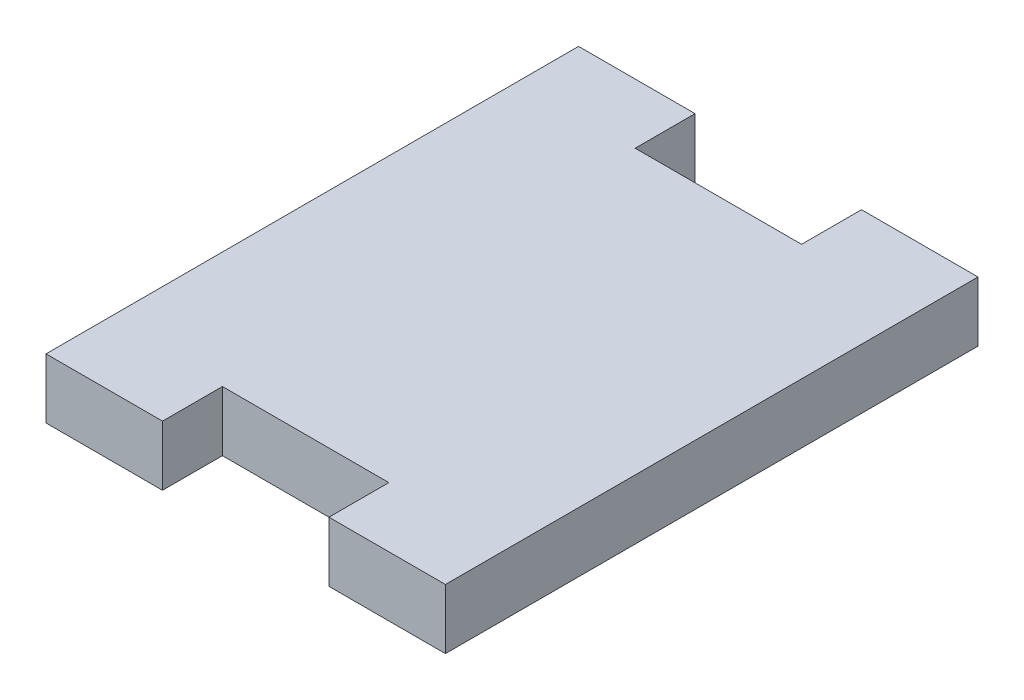
SolidWorks part; units mm, degrees
ref_plane "Front Plane" through (0, 0, 0) normal (0, 0, 1) x (1, 0, 0)
ref_plane "Top Plane" through (0, 0, 0) normal (0, 1, 0) x (1, 0, 0)
ref_plane "Right Plane" through (0, 0, 0) normal (1, 0, 0) x (0, 0, -1)
sketch "Sketch1" plane through (0, 0, 0) normal (0, 1, 0) x (1, 0, 0)
  line L0 (-363.1089, 480) -> (-363.1089, -480)
  line L1 (-363.1089, -480) -> (-303.1089, -480)
  line L2 (-303.1089, -480) -> (-303.1089, -400)
  line L3 (-303.1089, -400) -> (303.1089, -50)
  line L4 (303.1089, -50) -> (1036.8911, -50)
  line L5 (1036.8911, -50) -> (1036.8911, 50) construction
  line L6 (1036.8911, 50) -> (303.1089, 50)
  line L7 (303.1089, 50) -> (-303.1089, 400)
  line L8 (-303.1089, 400) -> (-303.1089, 480)
  line L9 (-303.1089, 480) -> (-363.1089, 480)
  line L10 (-363.1089, 0) -> (1036.8911, 0) construction
  line L11 (0, 225) -> (0, -225) construction
  line L14 (1036.8911, 50) -> (1066.8911, 50)
  line L15 (1036.8911, 50) -> (1036.8911, -50) construction
  line L16 (1036.8911, -50) -> (1066.8911, -50)
  line L17 (1066.8911, 50) -> (1066.8911, -50)
  dimension "D1" = 960
  dimension "D2" = 60
  dimension "D3" = 100
  dimension "D4" = 1400
  dimension "D5" = 150
  dimension "D6" = 80
  dimension "D7" = 30
extrude "Boss-Extrude1" add sketch "Sketch1" along normal blind 9
sketch "Sketch2" plane through (0, 9, 0) normal (0, 1, 0) x (1, 0, 0)
  line L1 (-363.1089, 480) -> (-303.1089, 480)
  line L2 (-363.1089, 480) -> (-363.1089, 400)
  line L3 (-363.1089, 400) -> (-303.1089, 400)
  line L4 (-303.1089, 480) -> (-303.1089, 400)
  line L5 (-363.1089, -480) -> (-303.1089, -480)
  line L6 (-363.1089, -480) -> (-363.1089, -400)
  line L7 (-363.1089, -400) -> (-303.1089, -400)
  line L8 (-303.1089, -480) -> (-303.1089, -400)
extrude "Boss-Extrude2" add sketch "Sketch2" along normal blind 500
sketch "Sketch3" plane through (0, 0, 0) normal (0, 0, 1) x (1, 0, 0)
  line L0 (-333.1089, 509) -> (-333.1089, 254.2) construction
  line L1 (-363.1089, 509) -> (-303.1089, 509) construction
  line L2 (-333.1089, 254.2) -> (-333.1089, 25) construction
  line L3 (-333.1089, 25) -> (-333.1089, 0) construction
  line L4 (-363.1089, 0) -> (-303.1089, 0) construction
  line L6 (-363.1089, 509) -> (-303.1089, 509)
  line L7 (-363.1089, 509) -> (-363.1089, 9)
  line L8 (-363.1089, 9) -> (-303.1089, 9)
  line L9 (-303.1089, 509) -> (-303.1089, 9)
  circle A0 centre (-333.1089, 254.2) radius 229.2
  circle A1 centre (-333.1089, 254.2) radius 6
  circle A2 centre (-333.1089, 254.2) radius 30
  dimension "D1" = 458.4
  dimension "D3" = 12
  dimension "D2" = 25
extrude "Cut-Extrude1" cut sketch "Sketch3" against normal through all both and the other way through all contours A2 L9 A0 L7 | A0 L9 L6 L7 | A1 region at (-333.1089, 495.8654, 0) region at (-333.1089, 380.1444, 0) region at (-333.1089, 254.2, 0)
sketch "Sketch4" plane through (0, 9, 0) normal (0, 1, 0) x (1, 0, 0)
  line L0 (866.8911, 25) -> (1066.8911, 25)
  line L2 (866.8911, -25) -> (1066.8911, -25)
  line L3 (1066.8911, -25) -> (1066.8911, 25)
  line L4 (866.8911, 0) -> (1066.8911, 0) construction
  line L5 (1066.8911, -50) -> (1066.8911, 50) construction
  circle A0 centre (866.8911, 0) radius 25
  dimension "D1" = 50
  dimension "D2" = 200
extrude "Cut-Extrude2" cut sketch "Sketch4" against normal through all contours L4 A0 L2 | A0 L4 L3 L0 | A0 region at (976.6223, 9, -12.7057) region at (884.0688, 9, -17.1777) region at (976.6223, 9, 12.7057)
sketch "Sketch16" plane through (0, 0, 0) normal (0, 0, 1) x (1, 0, 0)
  line L0 (-359.656, 240.2268) -> (-348.1089, 218.2888)
  line L5 (-348.1089, 218.2888) -> (-348.1089, 24)
  line L7 (-363.1089, 9) -> (-288.1089, 9)
  line L8 (303.1089, 9) -> (-303.1089, 9) construction
  line L9 (-303.1089, 254.2) -> (-303.1089, 24)
  line L10 (-348.1089, 24) -> (-363.1089, 9)
  line L11 (-303.1089, 254.2) -> (-303.1089, 9) construction
  line L12 (-303.1089, 24) -> (-288.1089, 9)
  line L13 (-348.1089, 24) -> (-303.1089, 24) construction
  line L14 (-346.3825, 247.2134) -> (-358.4836, 270.2039)
  line L15 (-319.8353, 261.1866) -> (-331.9364, 284.1771)
  circle A0 centre (-333.1089, 254.2) radius 15
  circle A1 centre (-333.1089, 254.2) radius 30
  arc A2 (-303.1089, 254.2) -> (-363.1089, 254.2) centre (-333.1089, 254.2) ccw construction
  circle A3 centre (-360.6089, 215.2) radius 12.5 construction
  dimension "D1" = 30
  dimension "D4" = 25
  dimension "D2" = 45
  dimension "D3" = 45
extrude "Boss-Extrude8" add sketch "Sketch16" along normal blind 305 and the other way blind 305 contours A1 L0 L5 L10 L7 L12 L9 | A1 L15 A0 L14 region at (-325.4564, 117.1914, 0) region at (-362.2383, 255.3393, 0)
sketch "Sketch17" plane through (0, 0, 0) normal (1, 0, 0) x (0, 0, -1)
  line L1 (230, 309) -> (-230, 309)
  line L2 (230, 309) -> (230, 9)
  line L3 (230, 9) -> (-230, 9)
  line L4 (-230, 309) -> (-230, 9)
  line L5 (0, 0) -> (0, 309) construction
  line L6 (480, 0) -> (-480, 0) construction
  dimension "D1" = 460
  dimension "D2" = 9
  dimension "D3" = 300
extrude "Cut-Extrude9" cut sketch "Sketch17" against normal through all
sketch "Sketch7" plane through (0, 0, 0) normal (1, 0, 0) x (0, 0, -1)
  line L1 (480, 284.2) -> (230, 284.2)
  line L2 (480, 284.2) -> (480, 9)
  line L3 (480, 9) -> (230, 9)
  line L4 (230, 284.2) -> (230, 9)
  line L5 (230, 218.2888) -> (230, 24) construction
  line L6 (471, 146.6) -> (444.5, 146.6) construction
  line L7 (480, 284.2) -> (471, 284.2)
  line L8 (480, 284.2) -> (480, 9)
  line L9 (480, 9) -> (471, 9)
  line L10 (471, 284.2) -> (471, 9)
  line L11 (400, 9) -> (409, 9)
  line L12 (400, 9) -> (400, 284.2)
  line L13 (400, 284.2) -> (409, 284.2)
  line L14 (409, 9) -> (409, 284.2)
  line L15 (444.5, 284.2) -> (435.5, 284.2)
  line L16 (444.5, 284.2) -> (444.5, 9)
  line L17 (444.5, 9) -> (435.5, 9)
  line L18 (435.5, 284.2) -> (435.5, 9)
  line L19 (444.5, 146.6) -> (435.5, 146.6) construction
  line L20 (435.5, 146.6) -> (409, 146.6) construction
  line L22 (0, 274.5241) -> (0, -136.9768) construction
  line L23 (-435.5, 146.6) -> (-409, 146.6) construction
  line L24 (305, 284.2) -> (296, 284.2)
  line L25 (305, 284.2) -> (305, 9)
  line L26 (305, 9) -> (296, 9)
  line L27 (296, 284.2) -> (296, 9)
  line L28 (239, 9) -> (230, 9)
  line L29 (239, 9) -> (239, 284.2)
  line L30 (239, 284.2) -> (230, 284.2)
  line L31 (230, 9) -> (230, 284.2)
  line L32 (-444.5, 146.6) -> (-435.5, 146.6) construction
  line L33 (-471, 146.6) -> (-444.5, 146.6) construction
  line L34 (-230, 9) -> (-230, 284.2)
  line L35 (-239, 284.2) -> (-230, 284.2)
  line L36 (-239, 9) -> (-239, 284.2)
  line L37 (-239, 9) -> (-230, 9)
  line L38 (-296, 284.2) -> (-296, 9)
  line L39 (-305, 9) -> (-296, 9)
  line L40 (-305, 284.2) -> (-305, 9)
  line L41 (-305, 284.2) -> (-296, 284.2)
  line L42 (-435.5, 284.2) -> (-435.5, 9)
  line L43 (-444.5, 9) -> (-435.5, 9)
  line L44 (-444.5, 284.2) -> (-444.5, 9)
  line L45 (-444.5, 284.2) -> (-435.5, 284.2)
  line L46 (-409, 9) -> (-409, 284.2)
  line L47 (-400, 284.2) -> (-409, 284.2)
  line L48 (-400, 9) -> (-400, 284.2)
  line L49 (-400, 9) -> (-409, 9)
  line L50 (-471, 284.2) -> (-471, 9)
  line L51 (-480, 9) -> (-471, 9)
  line L52 (-480, 284.2) -> (-480, 9)
  line L53 (-480, 284.2) -> (-471, 284.2)
  line L54 (-230, 284.2) -> (-230, 9)
  line L55 (-480, 9) -> (-230, 9)
  line L56 (-480, 284.2) -> (-480, 9)
  line L57 (-480, 284.2) -> (-230, 284.2)
  line L58 (305, 218.2888) -> (305, 24) construction
  dimension "D1" = 9
  dimension "D2" = 9
  dimension "D3" = 9
  dimension "D4" = 9
  dimension "D5" = 9
extrude "Cut-Extrude4" cut sketch "Sketch7" against normal through all both and the other way through all contours L1 L16 L3 L10 | L18 L1 L14 L3 | L29 L3 L27 L1 | L57 L38 L55 L36 | L57 L42 L55 L46 | L57 L50 L55 L44 | L1 L18 L3 L16 | L45 L44 L43 L42 region at (0, 146.6, -457.75) region at (0, 146.6, -440) region at (0, 146.6, -422.25) region at (0, 146.6, -267.5) region at (0, 146.6, 267.5) region at (0, 146.6, 422.25) region at (0, 146.6, 440) region at (0, 146.6, 457.75)
sketch "Sketch10" plane through (0, 9, 0) normal (0, 1, 0) x (1, 0, 0)
  line L0 (-363.1089, 221) -> (-113.0718, 221)
  line L2 (-113.0718, 221) -> (269.7114, 0)
  line L3 (269.7114, 0) -> (-113.0718, -221)
  line L4 (-113.0718, -221) -> (-363.1089, -221)
  line L5 (-363.1089, -221) -> (-363.1089, 221)
  line L6 (0, 0) -> (269.7114, 0) construction
  line L7 (-363.1089, 0) -> (0, 0) construction
  line L8 (-113.0718, -221) -> (-113.0718, 221) construction
  line L9 (303.1089, 50) -> (-303.1089, 400) construction
  line L10 (-363.1089, -230) -> (-363.1089, 230) construction
  line L11 (303.1089, 50) -> (337.7499, 30)
  line L12 (337.7499, 30) -> (806.8911, 30)
  line L13 (806.8911, 30) -> (841.5321, 50)
  line L14 (1066.8911, 50) -> (303.1089, 50) construction
  line L15 (841.5321, 50) -> (303.1089, 50)
  line L16 (303.1089, -50) -> (337.7499, -30)
  line L17 (337.7499, -30) -> (806.8911, -30)
  line L18 (806.8911, -30) -> (841.5321, -50)
  line L19 (303.1089, -50) -> (1066.8911, -50) construction
  line L20 (841.5321, -50) -> (303.1089, -50)
  line L21 (337.7499, -30) -> (337.7499, 30) construction
  line L22 (269.7114, 0) -> (337.7499, 0) construction
  line L23 (806.8911, 30) -> (806.8911, -30) construction
  line L24 (-303.1089, -400) -> (303.1089, -50) construction
  line L25 (841.5321, 50) -> (841.5321, -50) construction
  line L27 (-363.1089, 230) -> (-288.1089, 230) construction
  line L28 (-363.1089, -230) -> (-288.1089, -230) construction
  arc A0 (866.8911, 25) -> (866.8911, -25) centre (866.8911, 0) ccw construction
  dimension "D1" = 60
  dimension "D2" = 30
  dimension "D3" = 60
  dimension "D4" = 60
  dimension "D5" = 9
  dimension "D6" = 9
extrude "Cut-Extrude6" cut sketch "Sketch10" against normal through all
sketch "Sketch11" plane through (-363.1089, 0, 0) normal (-1, 0, 0) x (0, 0, 1)
  line L0 (-480, 254.2) -> (-480, 0) construction
  line L1 (-480, 224.2) -> (-400, 224.2)
  line L2 (-480, 224.2) -> (-480, 215.2)
  line L3 (-480, 215.2) -> (-400, 215.2)
  line L4 (-400, 224.2) -> (-400, 215.2)
  line L5 (-400, 254.2) -> (-400, 9) construction
  line L6 (400, 254.2) -> (400, 9) construction
  line L7 (400, 224.2) -> (480, 224.2)
  line L8 (400, 224.2) -> (400, 215.2)
  line L9 (400, 215.2) -> (480, 215.2)
  line L10 (480, 224.2) -> (480, 215.2)
  line L11 (480, 254.2) -> (480, 0) construction
  line L12 (-400, 224.2) -> (400, 224.2) construction
  line L13 (400, 215.2) -> (-400, 215.2) construction
  line L14 (-400, 284.2) -> (-409, 284.2) construction
  dimension "D1" = 9
  dimension "D2" = 60
extrude "Boss-Extrude5" add sketch "Sketch11" against normal up to surface (60 mm away) up to face at (-303.1089, 115.9778, 435.5556)
sketch "Sketch18" plane through (-348.1089, 0, 0) normal (-1, 0, 0) x (0, 0, 1)
  line L0 (-230, 218.2888) -> (-230, 24) construction
  line L1 (-305, 218.2888) -> (-230, 218.2888)
  line L2 (-305, 218.2888) -> (-305, 209.2888)
  line L3 (-305, 209.2888) -> (-230, 209.2888)
  line L4 (-230, 218.2888) -> (-230, 209.2888)
  line L5 (230, 24) -> (230, 218.2888) construction
  line L6 (305, 218.2888) -> (230, 218.2888)
  line L7 (305, 218.2888) -> (305, 209.2888)
  line L8 (305, 209.2888) -> (230, 209.2888)
  line L9 (230, 218.2888) -> (230, 209.2888)
  dimension "D1" = 9
  dimension "D2" = 9
extrude "Boss-Extrude9" add sketch "Sketch18" against normal up to surface (45 mm away) up to face at (-303.1089, 139.1, -234.5)
sketch "Sketch12" plane through (0, 9, 0) normal (0, 1, 0) x (1, 0, 0)
  line L0 (-363.1089, -480) -> (-303.1089, -480) construction
  line L1 (-363.1089, 480) -> (-303.1089, 480)
  line L2 (-363.1089, 480) -> (-363.1089, 489)
  line L3 (-363.1089, 489) -> (-303.1089, 489)
  line L4 (-303.1089, 480) -> (-303.1089, 489)
  line L5 (-363.1089, -480) -> (-303.1089, -480)
  line L6 (-363.1089, -480) -> (-363.1089, -489)
  line L7 (-363.1089, -489) -> (-303.1089, -489)
  line L8 (-303.1089, -480) -> (-303.1089, -489)
  dimension "D1" = 9
  dimension "D2" = 9
extrude "Boss-Extrude6" add sketch "Sketch12" against normal blind 9
fillet "Fillet3" radius 9 27 edges at (-303.1089, 4.5, -489) (-363.1089, 4.5, -489) (-363.1089, 4.5, -221) (-363.1089, 4.5, 221) (-363.1089, 4.5, 489) (-303.1089, 4.5, 489) (841.5321, 4.5, 50) (806.8911, 4.5, 30) (841.5321, 4.5, -50) (806.8911, 4.5, -30) (337.7499, 4.5, -30) (337.7499, 4.5, 30) (269.7114, 4.5, 0) (-113.0718, 4.5, 221) (-113.0718, 4.5, -221) (-303.1089, 24, -234.5) (-303.1089, 24, -300.5) (-303.1089, 24, 234.5) (-303.1089, 24, 300.5) (-348.1089, 24, 234.5) (-348.1089, 24, 300.5) (-348.1089, 24, -234.5) (-348.1089, 24, -300.5) (1066.8911, 4.5, 50) (1066.8911, 4.5, 25) (1066.8911, 4.5, -25) (1066.8911, 4.5, -50)
sketch "Sketch15" plane through (0, 9, 0) normal (0, 1, 0) x (1, 0, 0)
  line L0 (-83.154, 230) -> (-83.154, -230)
  line L1 (-113.154, 230) -> (-113.154, 220.6933) construction
  line L2 (-363.1089, 230) -> (-288.1089, 230) construction
  line L4 (-83.154, -230) -> (-143.154, -230)
  line L5 (-143.154, -230) -> (-143.154, 230)
  line L6 (-143.154, 230) -> (-83.154, 230)
  line L7 (0, 0) -> (-83.154, 0) construction
  arc A0 (-110.9833, 219.7942) -> (-115.4833, 221) centre (-115.4833, 212) ccw construction
  dimension "D1" = 60
extrude "Boss-Extrude7" add sketch "Sketch15" against normal blind 9
fillet "Fillet4" radius 9 4 edges at (-83.154, 4.5, -203.7269) (-83.154, 4.5, 203.7269) (-143.154, 4.5, 221) (-143.154, 4.5, -221)
sketch "Sketch20" plane through (0, 9, 0) normal (0, 1, 0) x (1, 0, 0)
  line L0 (-348.1089, 480) -> (-348.1089, 400)
  line L1 (-363.1089, 480) -> (-303.1089, 480)
  line L2 (-363.1089, 480) -> (-363.1089, 471)
  line L3 (-363.1089, 471) -> (-303.1089, 471)
  line L4 (-303.1089, 480) -> (-303.1089, 471)
  line L5 (-363.1089, 409) -> (-303.1089, 409)
  line L6 (-363.1089, 409) -> (-363.1089, 400)
  line L7 (-363.1089, 400) -> (-303.1089, 400)
  line L8 (-303.1089, 409) -> (-303.1089, 400)
  line L9 (-363.1089, 305) -> (-288.1089, 305)
  line L10 (-363.1089, 305) -> (-363.1089, 296)
  line L11 (-363.1089, 296) -> (-288.1089, 296)
  line L12 (-288.1089, 305) -> (-288.1089, 296)
  line L13 (-363.1089, 239) -> (-288.1089, 239)
  line L14 (-363.1089, 239) -> (-363.1089, 230)
  line L15 (-363.1089, 230) -> (-288.1089, 230)
  line L16 (-288.1089, 239) -> (-288.1089, 230)
  line L17 (-318.1089, 480) -> (-318.1089, 400)
  line L18 (-363.1089, 440) -> (-348.1089, 440) construction
  line L19 (-363.1089, 409) -> (-363.1089, 471) construction
  line L20 (-348.1089, 440) -> (-318.1089, 440) construction
  line L21 (-318.1089, 440) -> (-303.1089, 440) construction
  line L22 (-303.1089, 471) -> (-303.1089, 409) construction
  line L23 (-340.6089, 305) -> (-340.6089, 230)
  line L24 (-310.6089, 305) -> (-310.6089, 230)
  line L25 (-288.1089, 296) -> (-288.1089, 239) construction
  line L26 (-363.1089, 267.5) -> (-340.6089, 267.5) construction
  line L27 (-363.1089, 296) -> (-363.1089, 239) construction
  line L28 (-340.6089, 267.5) -> (-310.6089, 267.5) construction
  line L29 (-310.6089, 267.5) -> (-288.1089, 267.5) construction
  line L30 (-512.4702, 0) -> (462.9433, 0) construction
  line L31 (-310.6089, -267.5) -> (-288.1089, -267.5) construction
  line L32 (-340.6089, -267.5) -> (-310.6089, -267.5) construction
  line L33 (-363.1089, -267.5) -> (-340.6089, -267.5) construction
  line L34 (-288.1089, -296) -> (-288.1089, -239) construction
  line L35 (-318.1089, -440) -> (-303.1089, -440) construction
  line L36 (-348.1089, -440) -> (-318.1089, -440) construction
  line L37 (-363.1089, -440) -> (-348.1089, -440) construction
  line L38 (-310.6089, -305) -> (-310.6089, -230)
  line L39 (-340.6089, -305) -> (-340.6089, -230)
  line L40 (-318.1089, -480) -> (-318.1089, -400)
  line L41 (-288.1089, -239) -> (-288.1089, -230)
  line L42 (-363.1089, -230) -> (-288.1089, -230)
  line L43 (-363.1089, -239) -> (-363.1089, -230)
  line L44 (-363.1089, -239) -> (-288.1089, -239)
  line L45 (-288.1089, -305) -> (-288.1089, -296)
  line L46 (-363.1089, -296) -> (-288.1089, -296)
  line L47 (-363.1089, -305) -> (-363.1089, -296)
  line L48 (-363.1089, -305) -> (-288.1089, -305)
  line L49 (-303.1089, -409) -> (-303.1089, -400)
  line L50 (-363.1089, -400) -> (-303.1089, -400)
  line L51 (-363.1089, -409) -> (-363.1089, -400)
  line L52 (-363.1089, -409) -> (-303.1089, -409)
  line L53 (-303.1089, -480) -> (-303.1089, -471)
  line L54 (-363.1089, -471) -> (-303.1089, -471)
  line L55 (-363.1089, -480) -> (-363.1089, -471)
  line L56 (-363.1089, -480) -> (-303.1089, -480)
  line L57 (-348.1089, -480) -> (-348.1089, -400)
  dimension "D1" = 30
  dimension "D2" = 30
sketch "Sketch21" plane through (0, 9, 0) normal (0, 1, 0) x (1, 0, 0)
  line L0 (1066.8911, 34) -> (1066.8911, 41) construction
  line L1 (-363.1089, 489) -> (1066.8911, 489)
  line L2 (-363.1089, 489) -> (-363.1089, -489)
  line L3 (-363.1089, -489) -> (1066.8911, -489)
  line L4 (1066.8911, 489) -> (1066.8911, -489)
  line L5 (-354.1089, -489) -> (-312.1089, -489) construction
  line L6 (-363.1089, -305) -> (-363.1089, -400) construction
  line L7 (-312.1089, 489) -> (-354.1089, 489) construction
extrude "Cut-Extrude10" cut sketch "Sketch21" against normal through all body kept at (-363.1089, 9, -471) body kept at (-350.7449, 21.364, 296)
extrude "Boss-Extrude10" add sketch "Sketch20" against normal blind 9 contours L2 L3 L0 L1 | L1 L17 L3 L4 | L5 L17 L7 L8 | L6 L7 L0 L5 | L43 L44 L39 L42 | L38 L44 L41 L42 | L38 L48 L45 L46 | L47 L48 L39 L46 region at (-355.6089, 9, -475.5) region at (-310.6089, 9, -475.5) region at (-355.6089, 9, -404.5) region at (-310.6089, 9, -404.5) region at (-299.3589, 9, 300.5) region at (-351.8589, 9, 300.5) region at (-299.3589, 9, 234.5) region at (-351.8589, 9, 234.5)
sketch "Sketch22" plane through (0, 224.2, 0) normal (0, 1, 0) x (1, 0, 0)
  line L0 (-363.1089, 440) -> (-345.6089, 440) construction
  line L1 (-363.1089, 480) -> (-303.1089, 480)
  line L2 (-363.1089, 480) -> (-363.1089, 400)
  line L3 (-363.1089, 400) -> (-303.1089, 400)
  line L4 (-303.1089, 480) -> (-303.1089, 400)
  line L5 (-345.6089, 480) -> (-320.6089, 480)
  line L6 (-345.6089, 480) -> (-345.6089, 400)
  line L7 (-345.6089, 400) -> (-320.6089, 400)
  line L8 (-320.6089, 480) -> (-320.6089, 400)
  line L9 (-345.6089, 440) -> (-320.6089, 440) construction
  line L10 (-320.6089, 440) -> (-303.1089, 440) construction
  line M13 (-303.1089, 471) -> (-363.1089, 471)
  line M15 (-363.1089, 409) -> (-303.1089, 409)
  dimension "D1" = 25
sketch "Sketch23" plane through (0, 218.2888, 0) normal (0, 1, 0) x (1, 0, 0)
  line L0 (-288.1089, -296) -> (-288.1089, -305) construction
  line L1 (-363.1089, -230) -> (-288.1089, -230)
  line L2 (-363.1089, -230) -> (-363.1089, -305)
  line L3 (-363.1089, -305) -> (-288.1089, -305)
  line L4 (-288.1089, -230) -> (-288.1089, -305)
  line L5 (-300.4729, -305) -> (-288.1089, -305) construction
  line L6 (-348.1089, -296) -> (-348.1089, -239) construction
  line L7 (-348.1089, -230) -> (-303.1089, -230)
  line L8 (-348.1089, -230) -> (-348.1089, -305)
  line L9 (-348.1089, -305) -> (-303.1089, -305)
  line L10 (-303.1089, -230) -> (-303.1089, -305)
  line L11 (-335.6089, -230) -> (-315.6089, -230)
  line L12 (-335.6089, -230) -> (-335.6089, -305)
  line L13 (-335.6089, -305) -> (-315.6089, -305)
  line L14 (-315.6089, -230) -> (-315.6089, -305)
  line L15 (-303.1089, -239) -> (-303.1089, -296) construction
  line L16 (-358.4836, -230) -> (-346.3825, -230) construction
  line L17 (-348.1089, -267.5) -> (-335.6089, -267.5) construction
  line L18 (-335.6089, -267.5) -> (-315.6089, -267.5) construction
  line L19 (-315.6089, -267.5) -> (-303.1089, -267.5) construction
  dimension "D1" = 20
extrude "Cut-Extrude11" cut sketch "Sketch23" against normal through all both and the other way through all contours L4 L3 L2 L1
extrude "Cut-Extrude12" cut sketch "Sketch22" against normal through all both and the other way through all contours L8 L1 L6 M13 | L8 L6 L3 M15 region at (-333.1089, 224.2, -475.5) region at (-333.1089, 224.2, -404.5)
sketch "Sketch24" plane through (-303.1089, 0, 0) normal (1, 0, 0) x (0, 0, -1)
  line L0 (400, 254.2) -> (400, 0) construction
  line L1 (400, 224.2) -> (480, 224.2)
  line L2 (400, 224.2) -> (400, 215.2)
  line L3 (400, 215.2) -> (480, 215.2)
  line L4 (480, 224.2) -> (480, 215.2)
  line L5 (480, 254.2) -> (480, 0) construction
  line L6 (471, 224.2) -> (409, 224.2) construction
  line L7 (409, 215.2) -> (471, 215.2) construction
  line L9 (400, 281.4718) -> (480, 281.4718)
  line L10 (400, 281.4718) -> (400, 0)
  line L11 (400, 0) -> (480, 0)
  line L12 (480, 281.4718) -> (480, 0)
  line M5 (400, 254.2) -> (400, 0)
  line M6 (400, 0) -> (409, 0)
  line M7 (409, 0) -> (409, 215.2)
  line M8 (409, 215.2) -> (471, 215.2)
  line M9 (471, 215.2) -> (471, 0)
  line M10 (471, 0) -> (480, 0)
  line M11 (480, 0) -> (480, 254.2)
  line M12 (480, 254.2) -> (471, 254.2)
  line M13 (471, 254.2) -> (471, 224.2)
  line M14 (471, 224.2) -> (409, 224.2)
  line M15 (409, 224.2) -> (409, 254.2)
  line M16 (409, 254.2) -> (400, 254.2)
extrude "Cut-Extrude14" cut sketch "Sketch24" against normal through all contours L1 M13 M11 M12 | L12 L9 L10 M16 M15 M14 M13 M12 | L1 M5 M15 M16 | L3 M9 M10 M11 | L11 M7 M9 M8 | L3 M5 M6 M7 region at (-303.1089, 239.2, -404.5) region at (-303.1089, 254.6577, -440) region at (-303.1089, 107.6, -404.5) region at (-303.1089, 239.2, -475.5) region at (-303.1089, 107.6, -440) region at (-303.1089, 107.6, -475.5)
